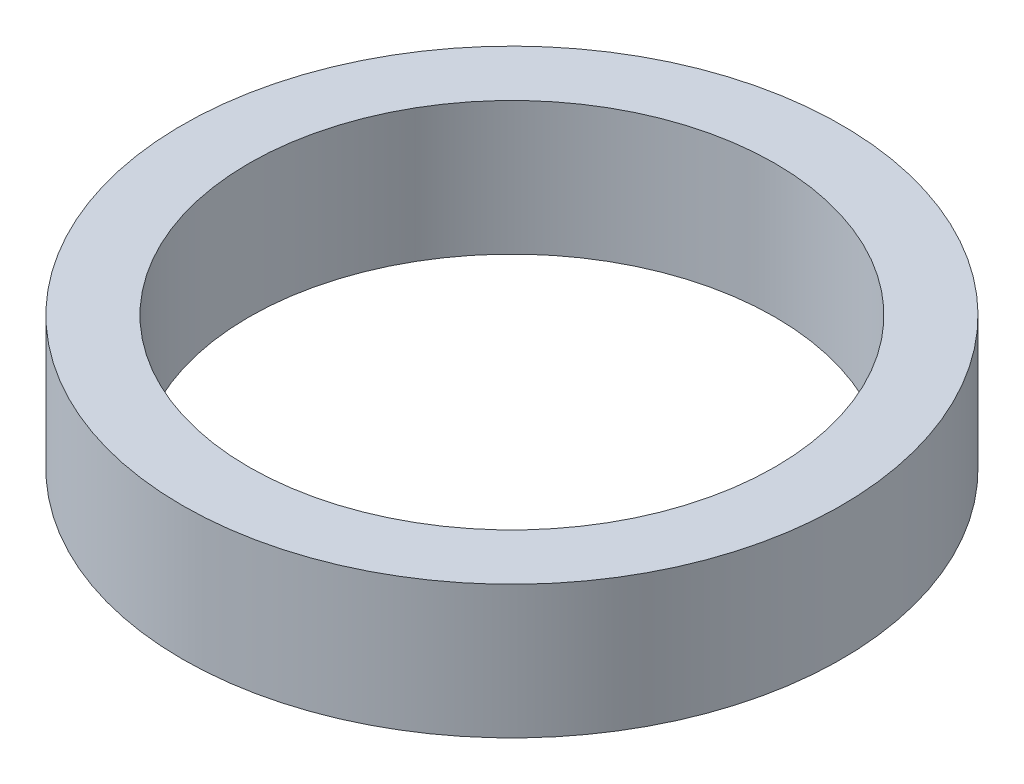
SolidWorks part; units mm, degrees
ref_plane "Front Plane" through (0, 0, 0) normal (0, 0, 1) x (1, 0, 0)
ref_plane "Top Plane" through (0, 0, 0) normal (0, 1, 0) x (1, 0, 0)
ref_plane "Right Plane" through (0, 0, 0) normal (1, 0, 0) x (0, 0, -1)
sketch "Sketch1" plane through (0, 0, 0) normal (0, 1, 0) x (1, 0, 0)
  circle A0 centre (0, 0) radius 15.725
  circle A1 centre (0, 0) radius 12.55
  dimension "D1" = 25.1
  dimension "D2" = 3.175
extrude "Boss-Extrude1" add sketch "Sketch1" along normal mid plane 6.35
